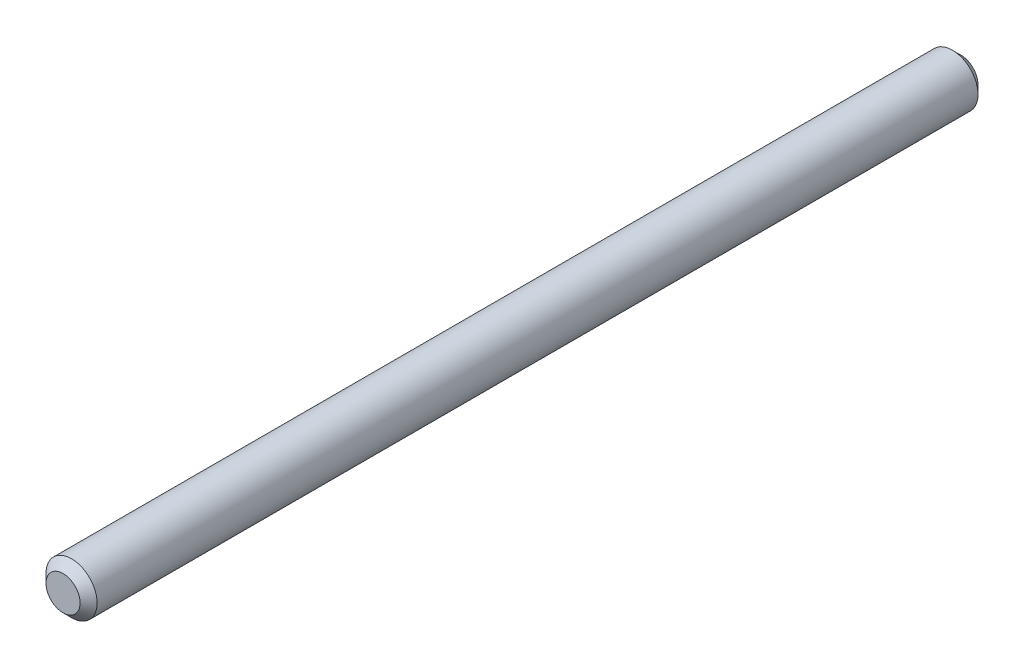
SolidWorks part; units mm, degrees
ref_plane "Płaszczyzna przednia" through (0, 0, 0) normal (0, 0, 1) x (1, 0, 0)
ref_plane "Płaszczyzna górna" through (0, 0, 0) normal (0, 1, 0) x (1, 0, 0)
ref_plane "Płaszczyzna prawa" through (0, 0, 0) normal (1, 0, 0) x (0, 0, -1)
sketch "Szkic1" plane through (0, 0, 0) normal (0, 0, 1) x (1, 0, 0)
  circle A0 centre (0, 0) radius 3
  dimension "D1" = 6
extrude "Dodanie-wyciągnięcie1" add sketch "Szkic1" along normal mid plane 80
chamfer "Sfazowanie1" distance 1 angle 45 2 edges at (3, 0, -40) (3, 0, 40)
extrude "Dodanie-wyciągnięcie2" add sketch "Szkic1<2>" along normal blind 25.4 and the other way up to surface from surface other way up to face at (3, 0, 39) starting at face at (2, 0, 40)
sketch "Szkic1<2>" plane through (0, 0, 0) normal (0, 0, 1) x (1, 0, 0) same geometry as "Szkic1"
chamfer "Sfazowanie2" distance 1 angle 45 1 edges at (3, 0, 65.4)
